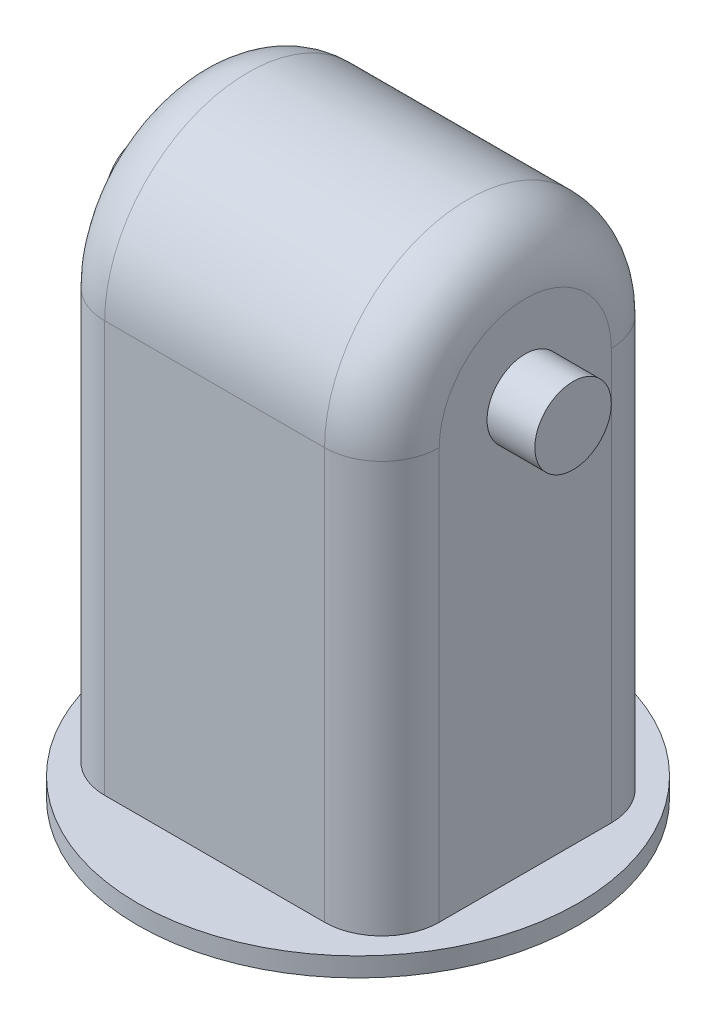
SolidWorks part; units mm, degrees
material "Plain Carbon Steel"
ref_plane "Front Plane" through (0, 0, 0) normal (0, 0, 1) x (1, 0, 0)
ref_plane "Top Plane" through (0, 0, 0) normal (0, 1, 0) x (1, 0, 0)
ref_plane "Right Plane" through (0, 0, 0) normal (1, 0, 0) x (0, 0, -1)
sketch "Sketch1" plane through (0, 0, 0) normal (0, 1, 0) x (1, 0, 0)
  line L1 (-17.5, -15) -> (17.5, -15)
  line L2 (-17.5, -15) -> (-17.5, 15)
  line L3 (-17.5, 15) -> (17.5, 15)
  line L4 (17.5, -15) -> (17.5, 15)
  line L5 (-17.5, -15) -> (17.5, 15) construction
  line L6 (-17.5, 15) -> (17.5, -15) construction
  point P0 (0, 0)
  dimension "D1" = 35
  dimension "D2" = 30
extrude "Boss-Extrude1" add sketch "Sketch1" along normal blind 60
sketch "Sketch2" plane through (17.5, 0, 0) normal (1, 0, 0) x (0, 0, -1)
  line L0 (-15, 0) -> (15, 0) construction
  circle A0 centre (0, 45) radius 4
  dimension "D1" = 8
  dimension "D2" = 45
extrude "Boss-Extrude2" add sketch "Sketch2" along normal blind 5
mirror "Mirror1" about plane through (0, 0, 0) normal (1, 0, 0) of "Boss-Extrude2"
sketch "Sketch4" plane through (0, 0, 0) normal (0, 1, 0) x (1, 0, 0)
  circle A0 centre (0, 0) radius 23.0489
extrude "Boss-Extrude3" add sketch "Sketch4" along normal blind 2
fillet "Fillet3" 2 edges at (0, 60, 15) (0, 60, -15) type full round first side face at (0, 31, 15) second side face at (0, 31, -15) middle face at (0, 60, 0)
fillet "Fillet1" radius 6 6 edges at (17.5, 23.5, -15) (-17.5, 23.5, -15) (-17.5, 23.5, 15) (17.5, 23.5, 15) (-17.5, 60, 0) (17.5, 60, 0)
sketch "Sketch7" plane through (0, 0, 0) normal (0, -1, 0) x (1, 0, 0)
  circle A0 centre (0, 0) radius 5
  dimension "D1" = 10
extrude "Boss-Extrude4" add sketch "Sketch7" along normal blind 1
